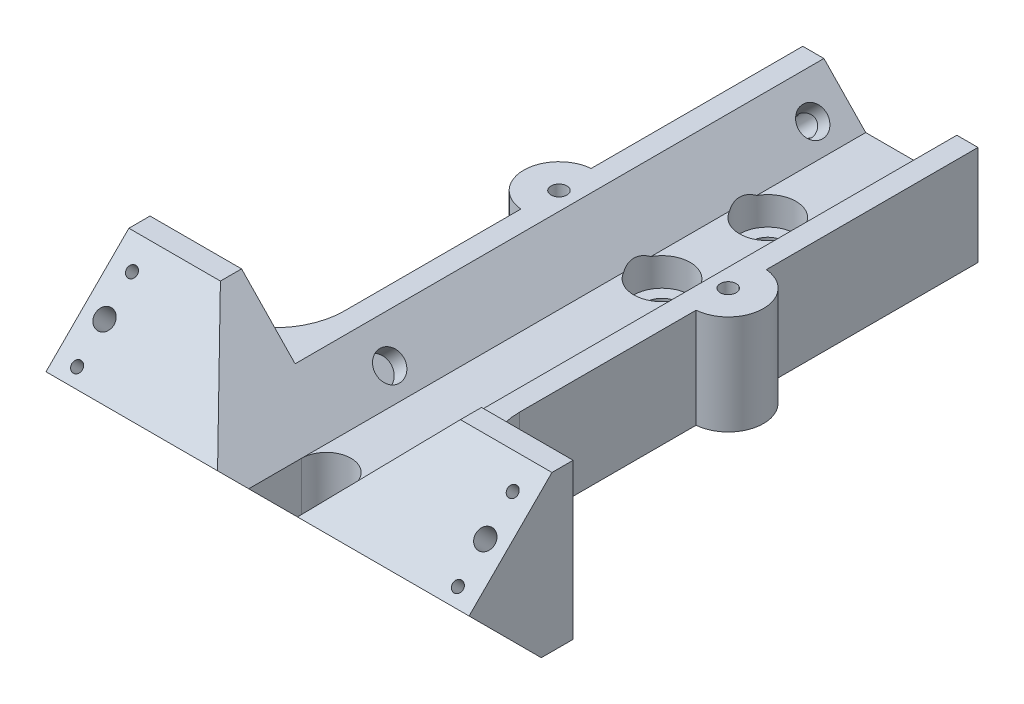
SolidWorks part; units mm, degrees
ref_plane "Front Plane" through (0, 0, 0) normal (0, 0, 1) x (1, 0, 0)
ref_plane "Top Plane" through (0, 0, 0) normal (0, 1, 0) x (1, 0, 0)
ref_plane "Right Plane" through (0, 0, 0) normal (1, 0, 0) x (0, 0, -1)
sketch "Sketch1" plane through (0, 0, 0) normal (0, 0, 1) x (1, 0, 0)
  line L0 (-3.5, 0) -> (3.5, 0)
  line L1 (3.5, 0) -> (9.425, 6.1355)
  line L2 (12.425, 6.1355) -> (12.425, -8)
  line L3 (12.425, -8) -> (-12.425, -8)
  line L4 (-12.425, -8) -> (-12.425, 6.1355)
  line L5 (-9.425, 6.1355) -> (-3.5, 0)
  line L6 (-9.425, 6.1355) -> (-12.425, 6.1355)
  line L7 (9.425, 6.1355) -> (12.425, 6.1355)
  dimension "D1" = 7
  dimension "D2" = 134
  dimension "D3" = 134
  dimension "D4" = 3
  dimension "D5" = 24.85
  dimension "D6" = 8
extrude "Boss-Extrude1" add sketch "Sketch1" along normal blind 75
sketch "Sketch2" plane through (0, 0, 75) normal (0, 0, 1) x (1, 0, 0)
  line L8 (-3.5, 0) -> (-9.425, 6.1355)
  line L9 (-9.425, 6.1355) -> (-12.425, 6.1355)
  line L10 (-12.425, 6.1355) -> (-12.425, -8)
  line L11 (-12.425, -8) -> (12.425, -8)
  line L12 (12.425, -8) -> (12.425, 6.1355)
  line L13 (12.425, 6.1355) -> (9.425, 6.1355)
  line L14 (9.425, 6.1355) -> (3.5, 0)
  line L15 (3.5, 0) -> (-3.5, 0)
  line L16 (-3.5, 0) -> (-9.425, 6.1355)
  line L17 (-9.425, 6.1355) -> (-30, 6.1355)
  line L18 (-30, 6.1355) -> (-30, -8)
  line L19 (-30, -8) -> (30, -8)
  line L20 (30, -8) -> (30, 6.1355)
  line L21 (30, 6.1355) -> (9.425, 6.1355)
  line L22 (9.425, 6.1355) -> (3.5, 0)
  line L23 (3.5, 0) -> (-3.5, 0)
  dimension "D2" = 60
  dimension "D1" = 0
extrude "Boss-Extrude2" add sketch "Sketch2" along normal blind 25
fillet "Fillet1" radius 10 2 edges at (12.425, -0.9322, 75) (-12.425, -0.9322, 75)
ref_plane "Plane2" through (0, 0, 85) normal (0, 0, 1) x (1, 0, 0)
sketch "Sketch3" plane through (30, 0, 0) normal (1, 0, 0) x (0, 0, -1)
  line L0 (-100, -8) -> (-85.8645, 6.1355)
  line L1 (-100, 6.1355) -> (-75, 6.1355) construction
  line L2 (-85.8645, 6.1355) -> (-100, 6.1355)
  line L3 (-100, 6.1355) -> (-100, -8)
  dimension "D1" = 45
extrude "Cut-Extrude1" cut sketch "Sketch3" against normal through all
hole_wizard "CBORE for M4 SHCS1" positions "Sketch4" profile "Sketch6" counterbore size "M4" standard "ANSI Metric" end condition through all
sketch "Sketch4" plane through (0, 0, 0) normal (0, 1, 0) x (1, 0, 0)
  point P0 (0, -17.39)
  point P2 (0, -32.39)
  dimension "D1" = 15
  dimension "D2" = 17.39
sketch "Sketch6" plane through (0, 0, 17.39) normal (1, 0, 0) x (0, 0, 1)
  line L0 (0, 0) -> (0, 8)
  line L1 (0, 8) -> (2.25, 8)
  line L3 (2.25, 8) -> (2.25, 4)
  line L4 (2.25, 4) -> (4, 4)
  line L5 (4, 4) -> (4, 0)
  line L7 (4, 0) -> (0, 0)
  line L11 (0, -6.35) -> (0, 107.95) construction
  dimension "Thru Hole Dia." = 4.5
  dimension "Thru Hole Depth" = 8
  dimension "C'Bore Dia." = 8
  dimension "C'Bore Depth" = 4
ref_plane "Plane1" through (0, 0, 5) normal (0, 0, -1) x (-1, 0, 0)
sketch "Sketch7" plane through (0, 0, 5) normal (0, 0, -1) x (-1, 0, 0)
  line L0 (-6.364, 2.246) -> (0, 8.61) construction
  line L1 (0, 8.61) -> (6.364, 2.246) construction
  line L2 (0, 8.61) -> (0, -14.6601) construction
  line L3 (3.5, 0) -> (9.425, 6.1355) construction
  line L4 (-9.425, 6.1355) -> (-3.5, 0) construction
  circle A0 centre (0, 8.61) radius 7 construction
  circle A1 centre (-6.364, 2.246) radius 2 construction
  circle A2 centre (6.364, 2.246) radius 2 construction
  point P9 (6.0104, 2.5996)
  point P12 (-6.0104, 2.5996)
  dimension "D1" = 14
  dimension "D2" = 4
  dimension "D3" = 45
  dimension "D4" = 45
  dimension "D5" = 0.5
sketch "Sketch8" plane through (1.8111, -1.7489, 0) normal (-0.7193, 0.6947, 0) x (0, 0, 1)
  circle A0 centre (5, 6.0452) radius 2
  dimension "D1" = 4
extrude "Cut-Extrude2" cut sketch "Sketch8" against normal blind 4
sketch "Sketch27" plane through (-1.8111, -1.7489, 0) normal (0.7193, 0.6947, 0) x (0, 0, -1)
  circle A0 centre (-5, 6.0452) radius 2
  dimension "D1" = 4
extrude "Cut-Extrude8" cut sketch "Sketch27" against normal blind 4
ref_plane "Plane5" through (0, 0, 65) normal (0, 0, -1) x (-1, 0, 0)
sketch "Sketch28" plane through (0, 0, 65) normal (0, 0, -1) x (-1, 0, 0)
  line L0 (-6.364, 2.246) -> (0, 8.61) construction
  line L1 (0, 8.61) -> (6.364, 2.246) construction
  line L2 (0, 0) -> (0, 8.61) construction
  line L3 (-4.6211, 1.1609) -> (-7.3997, 4.0383) construction
  line L4 (7.3997, 4.0383) -> (4.6211, 1.1609) construction
  circle A0 centre (0, 8.61) radius 7 construction
  circle A1 centre (-6.364, 2.246) radius 2 construction
  circle A2 centre (6.364, 2.246) radius 2 construction
  point P9 (-6.0104, 2.5996)
  point P10 (6.0104, 2.5996)
  dimension "D1" = 14
  dimension "D2" = 4
  dimension "D3" = 45
  dimension "D4" = 45
sketch "Sketch29" plane through (-1.8111, -1.7489, 0) normal (0.7193, 0.6947, 0) x (0, 0, -1)
  circle A0 centre (-65, 6.0452) radius 2
  dimension "D1" = 4
extrude "Cut-Extrude9" cut sketch "Sketch29" against normal blind 2.5
sketch "Sketch30" plane through (1.8111, -1.7489, 0) normal (-0.7193, 0.6947, 0) x (0, 0, 1)
  circle A0 centre (65, 6.0452) radius 2
  dimension "D1" = 4
extrude "Cut-Extrude10" cut sketch "Sketch30" against normal blind 2.5
hole_wizard "#6-32 Tapped Hole4" positions "Sketch31" profile "Sketch32" tap size "#6-32" standard "ANSI Inch"
sketch "Sketch31" plane through (0, 0, 0) normal (0, 0, -1) x (-1, 0, 0)
  line L0 (0, 8.61) -> (-8.4853, 0.1247) construction
  line L2 (0, 8.61) -> (8.4853, 0.1247) construction
  point P0 (-8.4853, 0.1247)
  point P2 (8.4853, 0.1247)
  dimension "D1" = 12
sketch "Sketch32" plane through (8.4853, 0.1247, 0) normal (1, 0, 0) x (0, 1, 0)
  line L0 (0, 0) -> (0, 10.2027)
  line L1 (0, 10.2027) -> (1.3525, 9.39)
  line L2 (1.3525, 9.39) -> (1.3525, 0)
  line L5 (1.3525, 0) -> (0, 0)
  line L10 (0, 10.2027) -> (-1.3526, 9.39) construction
  line L11 (0, -6.35) -> (0, 107.95) construction
  dimension "Tap Drill Dia." = 2.7051
  dimension "Tap Drill Depth" = 9.39
  dimension "Drill Angle" = 118
cosmetic thread "Hole Thread10" parameters "D1"=7.01, "D2"=3.5052
cosmetic thread "Hole Thread11" parameters "D1"=7.01, "D2"=3.5052
sketch "Sketch33" plane through (0, 6.1355, 0) normal (0, 1, 0) x (1, 0, 0)
  line L0 (0, -65) -> (0, -5) construction
  line L1 (7.7745, -5) -> (-7.7745, -5) construction
  line L2 (7.7745, -65) -> (-7.7745, -65) construction
  line L4 (-12, -35) -> (12, -35) construction
  line L5 (-12.425, -30.0181) -> (-12.425, -39.9819)
  line L6 (-12.425, -65) -> (-12.425, 0) construction
  line L7 (12.425, -30.0181) -> (12.425, -39.9819)
  line L8 (12.425, -65) -> (12.425, 0) construction
  arc A0 (-12.425, -30.0181) -> (-12.425, -39.9819) centre (-12, -35) ccw
  arc A1 (12.425, -39.9819) -> (12.425, -30.0181) centre (12, -35) ccw
  point P7 (0, -35)
  dimension "D2" = 10
  dimension "D1" = 24
extrude "Boss-Extrude4" add sketch "Sketch33" against normal up to surface (14.1355 mm away) up to face at (0, -8, 19.64)
hole_wizard "#4-40 Tapped Hole1" positions "Sketch34" profile "Sketch36" tap size "#4-40" standard "ANSI Inch" end condition through all
sketch "Sketch34" plane through (0, 6.1355, 0) normal (0, 1, 0) x (1, 0, 0)
  point P0 (-12, -35)
  point P3 (12, -35)
sketch "Sketch36" plane through (-12, 6.1355, 35) normal (1, 0, 0) x (0, 0, 1)
  line L0 (0, 0) -> (0, 14.1355)
  line L1 (0, 14.1355) -> (1.1303, 14.1355)
  line L2 (1.1303, 14.1355) -> (1.1303, 0)
  line L5 (1.1303, 0) -> (0, 0)
  line L11 (0, -6.35) -> (0, 107.95) construction
  dimension "Thru Tap Drill Dia." = 2.2606
  dimension "Thru Tap Drill Depth" = 14.1355
cosmetic thread "Hole Thread12" parameters "D2"=2.8448
cosmetic thread "Hole Thread13" parameters "D2"=2.8448
sketch "Sketch9" plane through (30, 0, 0) normal (1, 0, 0) x (0, 0, -1)
  line L0 (-85.8645, 6.1355) -> (-78, 14)
  line L1 (-78, 14) -> (-75, 14)
  line L2 (-75, 14) -> (-75, 6.1355)
  line L3 (-75, 6.1355) -> (-85.8645, 6.1355)
  line L4 (-100, -8) -> (-85.8645, 6.1355) construction
  dimension "D1" = 3
extrude "Boss-Extrude3" add sketch "Sketch9" against normal up to surface (60 mm away) up to face at (-30, -0.9322, 83.9661)
sketch "Sketch10" plane through (30, 0, 0) normal (1, 0, 0) x (0, 0, -1)
  line L0 (-100, -8) -> (-98, -6)
  line L1 (-100, -8) -> (-78, 14) construction
  line L2 (-98, -6) -> (-98, -8)
  line L3 (-100, -8) -> (-75, -8) construction
  line L4 (-98, -8) -> (-100, -8)
  dimension "D1" = 2
extrude "Cut-Extrude3" cut sketch "Sketch10" against normal through all
sketch "Sketch11" plane through (0, 0, 0) normal (0, 0, -1) x (-1, 0, 0)
  line L0 (-3.5, 0) -> (3.5, 0)
  line L1 (3.5, 0) -> (17.0196, 14)
  line L2 (30, 14) -> (-30, 14) construction
  line L3 (17.0196, 14) -> (-17.0196, 14)
  line L4 (-17.0196, 14) -> (-3.5, 0)
  line L5 (-9.425, 6.1355) -> (-3.5, 0) construction
  line L6 (3.5, 0) -> (9.425, 6.1355) construction
extrude "Cut-Extrude4" cut sketch "Sketch11" against normal through all
sketch "Sketch12" plane through (0, 0, 0) normal (0, 1, 0) x (1, 0, 0)
  line L0 (3.5, -80) -> (3.5, -92)
  line L1 (3.5, -92) -> (-3.5, -92)
  line L2 (-3.5, -92) -> (-3.5, -80)
  arc A0 (3.5, -80) -> (-3.5, -80) centre (0, -80) ccw
  dimension "D1" = 12
extrude "Cut-Extrude5" cut sketch "Sketch12" against normal through all
ref_plane "Plane3" through (0, 8.61, 0) normal (0, 1, 0) x (1, 0, 0)
ref_axis "Axis1" through (8.775, 8.61, 83.39) along (1, 0, 0)
ref_axis "Axis2" through (0, 8.61, 5) along (0, 0, 1)
ref_plane "Plane4" through (0, 47.0607, 47.0607) normal (0, 0.7071, 0.7071) x (1, 0, 0)
ref_point "Point1"
hole_wizard "#6-32 Tapped Hole3" positions "Sketch21" profile "Sketch22" tap size "#6-32" standard "ANSI Inch" end condition through all
sketch "Sketch21" plane through (0, 47.0607, 47.0607) normal (0, 0.7071, 0.7071) x (1, 0, 0)
  line L0 (-27, -54.3774) -> (27, -54.3774) construction
  point P1 (-27, -54.3774)
  point P2 (27, -54.3774)
  dimension "D1" = 54
sketch "Sketch22" plane through (-27, 8.61, 85.5113) normal (1, 0, 0) x (0, -0.7071, 0.7071)
  line L0 (0, 0) -> (0, 72.2107)
  line L1 (0, 72.2107) -> (1.3525, 72.2107)
  line L2 (1.3525, 72.2107) -> (1.3525, 0)
  line L5 (1.3525, 0) -> (0, 0)
  line L11 (0, -6.35) -> (0, 107.95) construction
  dimension "Thru Tap Drill Dia." = 2.7051
  dimension "Thru Tap Drill Depth" = 72.2107
cosmetic thread "Hole Thread4" parameters "D2"=3.5052
cosmetic thread "Hole Thread5" parameters "D2"=3.5052
hole_wizard "#1-72 Tapped Hole1" positions "Sketch23" profile "Sketch24" tap size "#1-72" standard "ANSI Inch" end condition through all
sketch "Sketch23" plane through (0, 47.0607, 47.0607) normal (0, 0.7071, 0.7071) x (1, 0, 0)
  line L2 (-27, -54.3774) -> (-27, -48.8774) construction
  line L4 (-27, -54.3774) -> (-27, -59.8774) construction
  line L6 (-30, -73.5391) -> (-30, -45.2548) construction
  line L7 (27, -54.3774) -> (27, -48.8774) construction
  line L9 (27, -59.8774) -> (27, -54.3774) construction
  point P0 (-27, -48.8774)
  point P2 (-27, -59.8774)
  point P4 (27, -48.8774)
  point P6 (27, -59.8774)
  dimension "D1" = 11
sketch "Sketch24" plane through (-27, 12.4991, 81.6222) normal (1, 0, 0) x (0, -0.7071, 0.7071)
  line L0 (0, 0) -> (0, 72.2107)
  line L1 (0, 72.2107) -> (0.7556, 72.2107)
  line L2 (0.7556, 72.2107) -> (0.7556, 0)
  line L5 (0.7556, 0) -> (0, 0)
  line L11 (0, -6.35) -> (0, 107.95) construction
  dimension "Thru Tap Drill Dia." = 1.5113
  dimension "Thru Tap Drill Depth" = 72.2107
cosmetic thread "Hole Thread6" parameters "D2"=1.8542
cosmetic thread "Hole Thread7" parameters "D2"=1.8542
cosmetic thread "Hole Thread8" parameters "D2"=1.8542
cosmetic thread "Hole Thread9" parameters "D2"=1.8542
sketch "Sketch26" plane through (0, 46, 46) normal (0, 0.7071, 0.7071) x (1, 0, 0)
  line L1 (-38.8625, -61.8774) -> (40.0948, -61.8774)
  line L2 (-38.8625, -61.8774) -> (-38.8625, -76.8232)
  line L3 (-38.8625, -76.8232) -> (40.0948, -76.8232)
  line L4 (40.0948, -61.8774) -> (40.0948, -76.8232)
  circle A0 centre (27, -54.3774) radius 1.3525 construction
  dimension "D1" = 7.5
extrude "Cut-Extrude7" cut sketch "Sketch26" against normal through all
sketch "Sketch37" plane through (0, 0, 0) normal (0, 1, 0) x (1, 0, 0)
  circle A0 centre (0, -17.39) radius 4 construction
  circle A1 centre (0, -17.39) radius 4
  circle A2 centre (0, -32.39) radius 4 construction
  circle A3 centre (0, -32.39) radius 4
extrude "Cut-Extrude11" cut sketch "Sketch37" along normal blind 10
